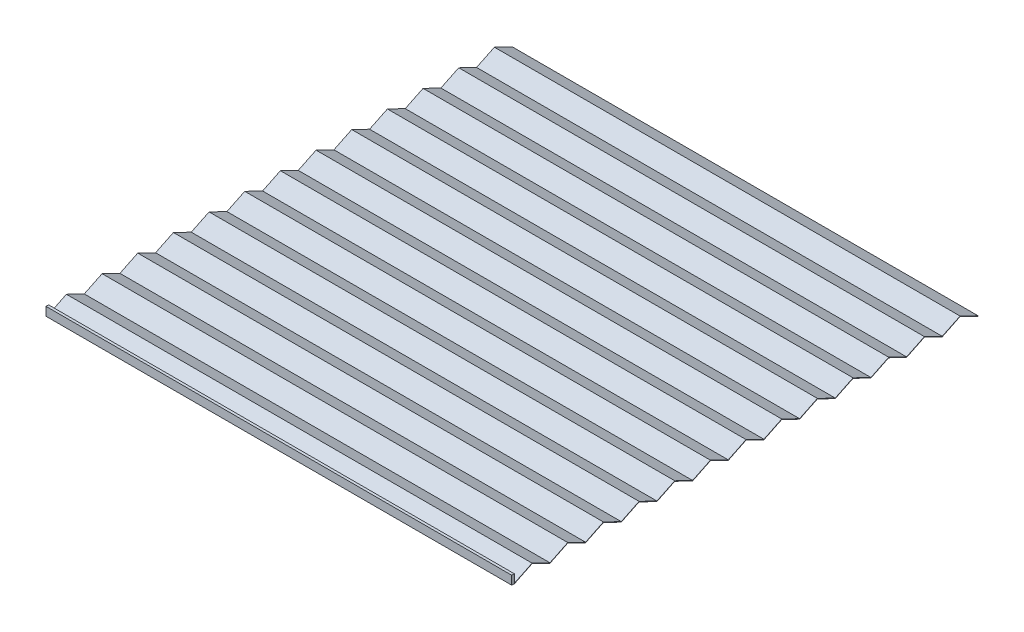
SolidWorks part; units mm, degrees
ref_plane "Front Plane" through (0, 0, 0) normal (0, 0, 1) x (1, 0, 0)
ref_plane "Top Plane" through (0, 0, 0) normal (0, 1, 0) x (1, 0, 0)
ref_plane "Right Plane" through (0, 0, 0) normal (1, 0, 0) x (0, 0, -1)
sketch "Sketch2" plane through (0, 0, 0) normal (0, 0, 1) x (1, 0, 0)
  line L1 (-270, 10) -> (270, 10)
  line L2 (-270, 10) -> (-270, 0)
  line L3 (-270, 0) -> (270, 0)
  line L4 (270, 10) -> (270, 0)
  point P4 (0, 0)
  dimension "D1" = 10
  dimension "D2" = 540
extrude "Boss-Extrude1" add sketch "Sketch2" along normal blind 3
sketch "Sketch3" plane through (270, 0, 0) normal (1, 0, 0) x (0, 0, -1)
  line L0 (0, 10) -> (537.6287, 10) construction
  line L1 (0, 0) -> (537.6287, 0) construction
  line L2 (537.6287, 10) -> (537.6287, 0) construction
  line L3 (0, 0) -> (20.678, 10)
  line L4 (20.678, 10) -> (41.3561, 0)
  line L5 (41.3561, 0) -> (62.0341, 10)
  line L6 (62.0341, 10) -> (82.7121, 0)
  line L7 (82.7121, 0) -> (103.3901, 10)
  line L8 (103.3901, 10) -> (124.0682, 0)
  line L9 (124.0682, 0) -> (144.7462, 10)
  line L10 (144.7462, 10) -> (165.4242, 0)
  line L11 (165.4242, 0) -> (186.1022, 10)
  line L12 (186.1022, 10) -> (206.7803, 0)
  line L13 (206.7803, 0) -> (227.4583, 10)
  line L14 (227.4583, 10) -> (248.1363, 0)
  line L15 (248.1363, 0) -> (268.8144, 10)
  line L16 (268.8144, 10) -> (289.4924, 0)
  line L17 (289.4924, 0) -> (310.1704, 10)
  line L18 (310.1704, 10) -> (330.8484, 0)
  line L20 (330.8484, 0) -> (351.5265, 10)
  line L21 (351.5265, 10) -> (372.2045, 0)
  line L22 (372.2045, 0) -> (392.8825, 10)
  line L23 (392.8825, 10) -> (413.5606, 0)
  line L24 (413.5606, 0) -> (434.2386, 10)
  line L25 (434.2386, 10) -> (454.9166, 0)
  line L26 (454.9166, 0) -> (475.5946, 10)
  line L27 (475.5946, 10) -> (496.2727, 0)
  line L28 (496.2727, 0) -> (516.9507, 10)
  line L29 (516.9507, 10) -> (537.6287, 0)
  line L30 (537.6287, 10) -> (537.6287, 0) construction
extrude "Extrude-Thin1" add sketch "Sketch3" against normal through all thin thin type mid plane wall 0.5
